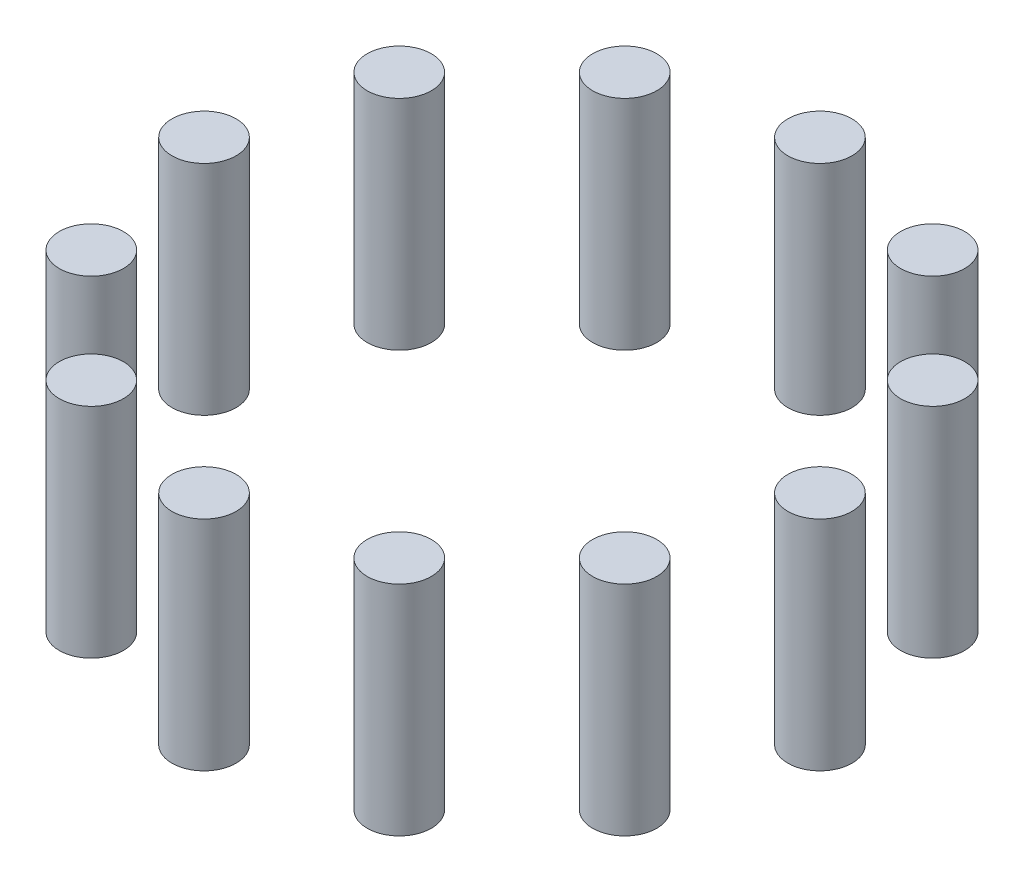
SolidWorks part; units mm, degrees
ref_plane "Front" through (0, 0, 0) normal (0, 0, 1) x (1, 0, 0)
ref_plane "Top" through (0, 0, 0) normal (0, 1, 0) x (1, 0, 0)
ref_plane "Right" through (0, 0, 0) normal (1, 0, 0) x (0, 0, -1)
sketch "Sketch1" plane through (0, 0, 0) normal (0, 1, 0) x (1, 0, 0)
  line L0 (0, 0) -> (0, 24) construction
  circle A0 centre (0, 24) radius 2.5
  circle A1 centre (12, 20.7846) radius 2.5
  circle A2 centre (20.7846, 12) radius 2.5
  circle A3 centre (24, 0) radius 2.5
  circle A4 centre (20.7846, -12) radius 2.5
  circle A5 centre (12, -20.7846) radius 2.5
  circle A6 centre (0, -24) radius 2.5
  circle A7 centre (-12, -20.7846) radius 2.5
  circle A8 centre (-20.7846, -12) radius 2.5
  circle A9 centre (-24, 0) radius 2.5
  circle A10 centre (-20.7846, 12) radius 2.5
  circle A11 centre (-12, 20.7846) radius 2.5
  dimension "D1" = 5
  dimension "D2" = 24
  dimension "D3" = 12
extrude "Boss-Extrude1" add sketch "Sketch1" along normal blind 17
ref_axis "Axis1" through (0, 50, 0) along (0, -1, 0)
